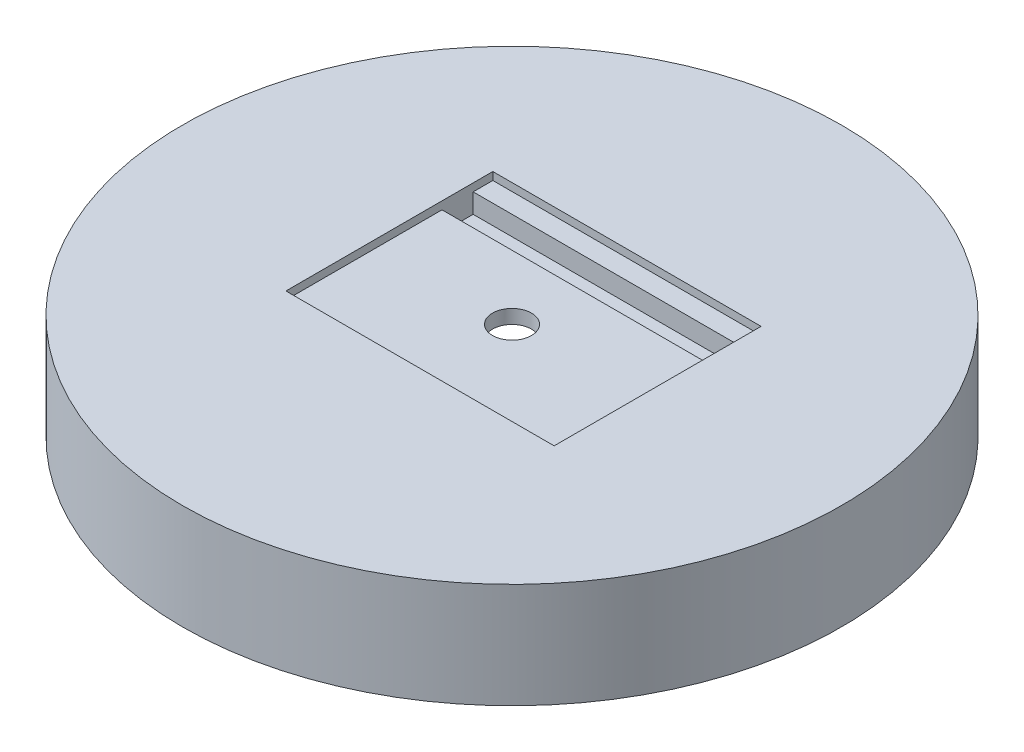
SolidWorks part; units mm, degrees
ref_plane "Front Plane" through (0, 0, 0) normal (0, 0, 1) x (1, 0, 0)
ref_plane "Top Plane" through (0, 0, 0) normal (0, 1, 0) x (1, 0, 0)
ref_plane "Right Plane" through (0, 0, 0) normal (1, 0, 0) x (0, 0, -1)
sketch "Sketch3" plane through (0, 0, 0) normal (0, 0, 1) x (1, 0, 0)
  line L0 (0, 0) -> (17.5, 0) construction
  line L2 (17.5, 0) -> (1.27, 5.4429)
  line L3 (1.27, -13.9932) -> (1.27, 1.2597) construction
  line L4 (0, 0) -> (0, -13.9932) construction
  line L5 (17.5, 0) -> (21.5, 0)
  line L6 (1.27, 6.858) -> (1.27, 5.4429)
  line L9 (21.5, 6.858) -> (21.5, 0)
  line L11 (21.5, 6.858) -> (1.27, 6.858)
  line L12 (1.27, 5.4429) -> (1.27, 6.858) construction
  dimension "D1" = 17.5
  dimension "D2" = 6.858
  dimension "D3" = 1.27
  dimension "D4" = 4
revolve "Revolve1" add sketch "Sketch3" angle 360 about L4
sketch "Sketch for side slot DNU" plane through (0, 0, 0) normal (0, 0, 1) x (1, 0, 0)
  line L0 (0, 0) -> (0, 18.8028) construction
  line L1 (0, 0) -> (-24.5114, 0) construction
  line L2 (-7.874, 8.382) -> (7.874, 8.382)
  line L3 (-7.874, 8.382) -> (-7.874, 9.398)
  line L4 (-7.874, 9.398) -> (7.874, 9.398)
  line L5 (7.874, 8.382) -> (7.874, 9.398)
  line L6 (-7.874, 8.382) -> (7.874, 9.398) construction
  line L7 (-7.874, 9.398) -> (7.874, 8.382) construction
  point P3 (0, 8.89)
  dimension "D1" = 15.748
  dimension "D2" = 1.016
  dimension "D3" = 8.89
ref_plane "Plane for board depression" through (0, 12.7, 0) normal (0, 1, 0) x (1, 0, 0)
sketch "Sketch5" plane through (0, 12.7, 0) normal (0, 1, 0) x (1, 0, 0)
  line L0 (0, 0) -> (35.335, 0) construction
  line L1 (0, 0) -> (0, 26.2568) construction
  line L2 (8.75, 7.5) -> (-8.75, 7.5)
  line L3 (-8.75, 7.5) -> (-8.75, -6)
  line L4 (-8.75, -6) -> (8.75, -6)
  line L5 (8.75, -6) -> (8.75, 7.5)
  point P7 (0, 7.5)
  dimension "D1" = 17.5
  dimension "D2" = 13.5
  dimension "D3" = 7.5
extrude "Cut-Extrude1" cut sketch "Sketch5" against normal blind 6.35
ref_plane "plane for header solder depression" through (0, 15.24, 0) normal (0, 1, 0) x (1, 0, 0)
sketch "Sketch6" plane through (0, 15.24, 0) normal (0, 1, 0) x (1, 0, 0)
  line L0 (0, 0) -> (0, 25.5996) construction
  line L1 (0, 0) -> (0, 26.2568) construction
  line L2 (31.19, 5.2) -> (-31.19, 5.2) construction
  line L3 (8.75, 7.5) -> (-8.75, 7.5) construction
  line L4 (8.75, 6.216) -> (-8.75, 6.216)
  line L5 (8.75, 4.184) -> (-8.75, 4.184)
  line L6 (-8.75, 6.216) -> (-8.75, 4.184)
  line L8 (8.75, 6.216) -> (8.75, 4.184)
  line L10 (31.19, 6.216) -> (-31.19, 6.216) construction
  line L11 (31.19, 4.184) -> (-31.19, 4.184) construction
  point P9 (0, 5.2)
  dimension "D1" = 2.3
  dimension "D2" = 1.016
  dimension "D3" = 1.016
extrude "Cut-Extrude2" cut sketch "Sketch6" against normal blind 10.16
